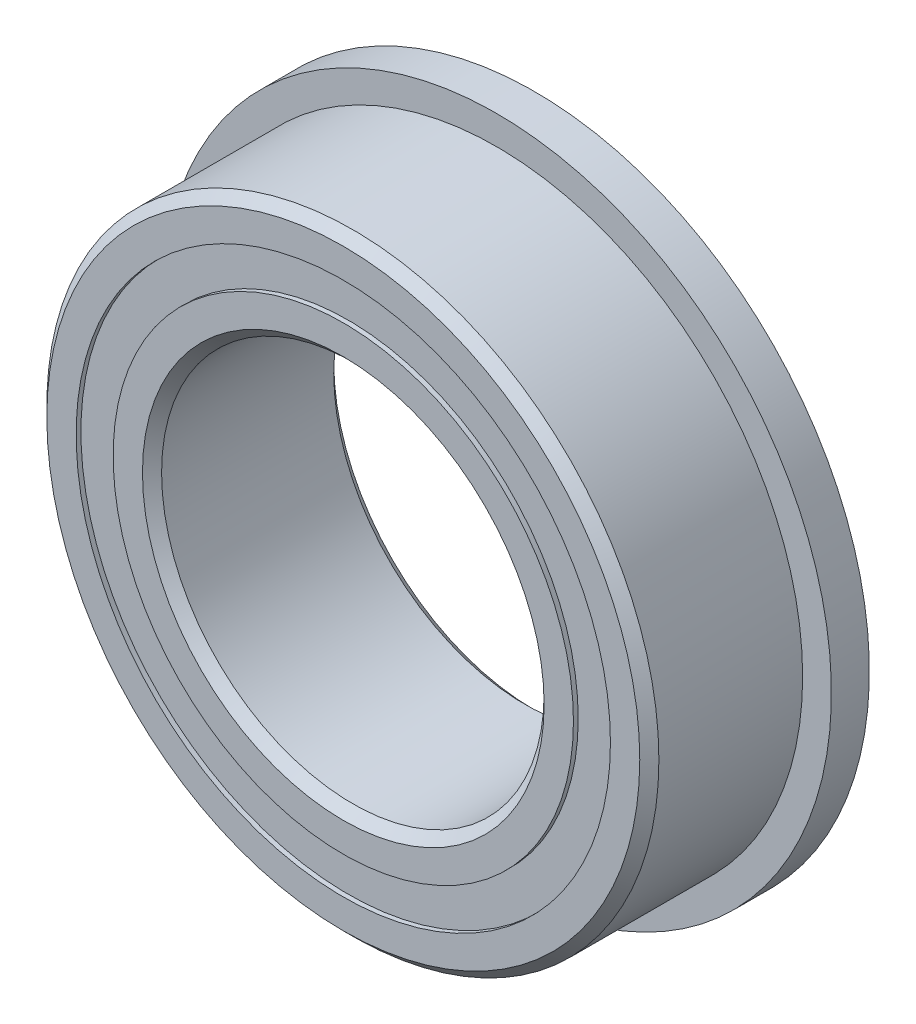
SolidWorks part; units mm, degrees
ref_plane "Front Plane" through (0, 0, 0) normal (0, 0, 1) x (1, 0, 0)
ref_plane "Top Plane" through (0, 0, 0) normal (0, 1, 0) x (1, 0, 0)
ref_plane "Right Plane" through (0, 0, 0) normal (1, 0, 0) x (0, 0, -1)
sketch "Sketch0" plane through (0, 0, 0) normal (1, 0, 0) x (0, 0, -1)
  line L0 (1.9844, 0) -> (-1.9844, 0) construction
  line L1 (0, 6.35) -> (0, -6.35) construction
  line L2 (0, 3.9688) -> (0, 6.35) construction
  line L3 (1.9844, 5.1594) -> (-1.9844, 5.1594) construction
  line L4 (-1.9844, 6.1516) -> (-1.7859, 6.35) construction
  line L5 (-1.7859, 6.35) -> (1.7859, 6.35) construction
  line L6 (1.7859, 6.35) -> (1.9844, 6.1516) construction
  line L7 (1.9844, 6.1516) -> (1.9844, 5.5432) construction
  line L8 (1.9844, 5.5432) -> (0.8819, 5.5432) construction
  line L9 (0.8819, 5.5432) -> (-0.8819, 5.5432) construction
  line L10 (-0.8819, 5.5432) -> (-1.9844, 5.5432) construction
  line L11 (-1.9844, 5.5432) -> (-1.9844, 6.1516) construction
  line L12 (-1.9844, 6.1516) -> (-1.7859, 6.1516) construction
  line L13 (-1.7859, 6.1516) -> (-1.7859, 6.35) construction
  line L14 (-0.9618, 5.1594) -> (0.9618, 5.1594) construction
  line L15 (-1.9844, 5.5432) -> (-1.9844, 0) construction
  line L16 (1.9844, 6.9469) -> (1.9844, 0) construction
  line L17 (1.9844, 6.9469) -> (1.197, 6.9469) construction
  circle A1 centre (0, 5.1594) radius 0.9618 construction
  point P4 (0, 0)
  point P5 (0, 0)
  point P9 (0, 5.1594)
  point P10 (0, 5.1594)
  point P15 (0, 5.5432)
  point P23 (0, 6.35)
  dimension "Flange OD" = 13.8938
  dimension "Th" = 0.7874
  dimension "OD" = 12.7
  dimension "Shaft Dia" = 7.9375
  dimension "Width" = 3.9688
  dimension "D4" = 0.1984
  dimension "D5" = 1.7639
  dimension "D6" = 0.3838
sketch "Sketch1" plane through (0, 0, 0) normal (1, 0, 0) x (0, 0, -1)
  line L0 (-1.9844, 0) -> (1.9844, 0) construction
  line L1 (0, 6.35) -> (0, -6.35) construction
  line L2 (1.7859, 6.35) -> (-1.7859, 6.35)
  line L3 (-1.7859, 6.35) -> (-1.9844, 6.1516)
  line L4 (-1.9844, 6.1516) -> (-1.9844, 5.5432)
  line L5 (-1.9844, 5.5432) -> (-0.8819, 5.5432)
  line L6 (1.9844, 5.5432) -> (0.8819, 5.5432)
  line L7 (1.9844, 6.1516) -> (1.9844, 5.5432)
  line L8 (1.7859, 6.35) -> (1.9844, 6.1516)
  line L9 (0, 6.35) -> (0, 5.1594) construction
  line L10 (0, 5.1594) -> (0, 3.9688) construction
  arc A0 (-0.8819, 5.5432) -> (0.8819, 5.5432) centre (0, 5.1594) cw
  circle A1 centre (0, 5.1594) radius 0.9618 construction
  point P14 (0, 3.9688)
revolve "Revolve1" add sketch "Sketch1" angle 360 about L0
sketch "Sketch3" plane through (0, 0, 0) normal (1, 0, 0) x (0, 0, -1)
  line L0 (-1.9844, 4.7756) -> (-0.8819, 4.7756)
  line L1 (0, 6.35) -> (0, -6.35) construction
  line L2 (-1.9844, 6.1516) -> (-1.9844, 5.5432) construction
  line L3 (-1.9844, 4.7756) -> (-1.9844, 4.1672)
  line L4 (-1.7859, 6.35) -> (-1.9844, 6.1516) construction
  line L5 (-1.9844, 4.1672) -> (-1.7859, 3.9688)
  line L6 (-1.7859, 3.9688) -> (1.7859, 3.9688)
  line L7 (1.7859, 6.35) -> (1.7859, -6.35) construction
  line L8 (1.7859, 3.9688) -> (1.9844, 4.1672)
  line L9 (1.9844, -6.1516) -> (1.9844, 6.1516) construction
  line L10 (1.9844, 4.1672) -> (1.9844, 4.7756)
  line L11 (1.9844, 4.7756) -> (0.8819, 4.7756)
  line L13 (1.7859, 6.35) -> (1.9844, 6.1516) construction
  arc A0 (0.8819, 5.5432) -> (-0.8819, 5.5432) centre (0, 5.1594) ccw construction
  arc A1 (0.8819, 4.7756) -> (-0.8819, 4.7756) centre (0, 5.1594) cw
revolve "Revolve3" add sketch "Sketch3" angle 360 about L0
sketch "Sketch4" plane through (0, 0, 0) normal (1, 0, 0) x (0, 0, -1)
  line L0 (-0.9618, 5.1594) -> (0.9618, 5.1594)
  arc A2 (-0.9618, 5.1594) -> (0.9618, 5.1594) centre (0, 5.1594) cw
  arc A3 (0.8819, 5.5432) -> (-0.8819, 5.5432) centre (0, 5.1594) ccw construction
revolve "Revolve4" add sketch "Sketch4" angle 360 about L0
ref_axis "Axis1" through (0, 0, -1.9844) along (0, 0, 1)
pattern_circular "CirPattern1" count 12 every 30 about axis through (0, 0, -1.9844) along (0, 0, 1) of bodies 104
sketch "Sketch5" plane through (0, 0, 0) normal (1, 0, 0) x (0, 0, -1)
  line L0 (-1.9844, 5.5432) -> (-0.8819, 5.5432) construction
  line L1 (-1.8852, 5.5432) -> (-0.9618, 5.5432)
  line L2 (-1.8852, 5.5432) -> (-1.8852, 4.7756)
  line L3 (-1.8852, 4.7756) -> (-0.9618, 4.7756)
  line L4 (-0.9618, 5.5432) -> (-0.9618, 4.7756)
  line L5 (-1.9844, 4.7756) -> (-0.8819, 4.7756) construction
  line L6 (1.9844, 5.5432) -> (0.8819, 5.5432) construction
  line L7 (1.8852, 5.5432) -> (0.9618, 5.5432)
  line L8 (1.8852, 5.5432) -> (1.8852, 4.7756)
  line L9 (1.8852, 4.7756) -> (0.9618, 4.7756)
  line L10 (0.9618, 5.5432) -> (0.9618, 4.7756)
  line L11 (1.9844, 4.7756) -> (0.8819, 4.7756) construction
  line L12 (-1.7859, 6.35) -> (-1.9844, 6.1516) construction
  point P18 (-1.8852, 6.2508)
revolve "Revolve5" add sketch "Sketch5" angle 360 about L0
sketch "Sketch6" plane through (0, 0, 0) normal (1, 0, 0) x (0, 0, -1)
  line L0 (1.9844, 0) -> (-1.9844, 0) construction
  line L1 (1.9844, 5.5432) -> (1.197, 5.5432)
  line L2 (1.9844, 5.5432) -> (1.9844, 6.9469)
  line L3 (1.9844, 6.9469) -> (1.197, 6.9469)
  line L4 (1.197, 5.5432) -> (1.197, 6.9469)
revolve "Revolve6" add sketch "Sketch6" angle 360 about L0
sketch "Ref1" plane through (0, 0, 0) normal (0, 0, 1) x (1, 0, 0)
  line L0 (-3.9688, 0) -> (3.9688, 0) construction
  point P4 (0, 0)
  dimension "ID" = 7.9375
equation "\"D2@CirPattern1\" = 360/\"Balls@CirPattern1\""
equation "\"D4@Sketch0\"=\"Width@Sketch0\"*.05"
equation "\"D5@Sketch0\"=\"Width@Sketch0\"/2.25"
equation "\"D6@Sketch0\"= ( ( ( \"OD@Sketch0\" - \"Width@Sketch0\" ) / 2 ) / 3.25 ) / 3.5"
equation "\"ID@Ref1\"=\"Shaft Dia@Sketch0\""
